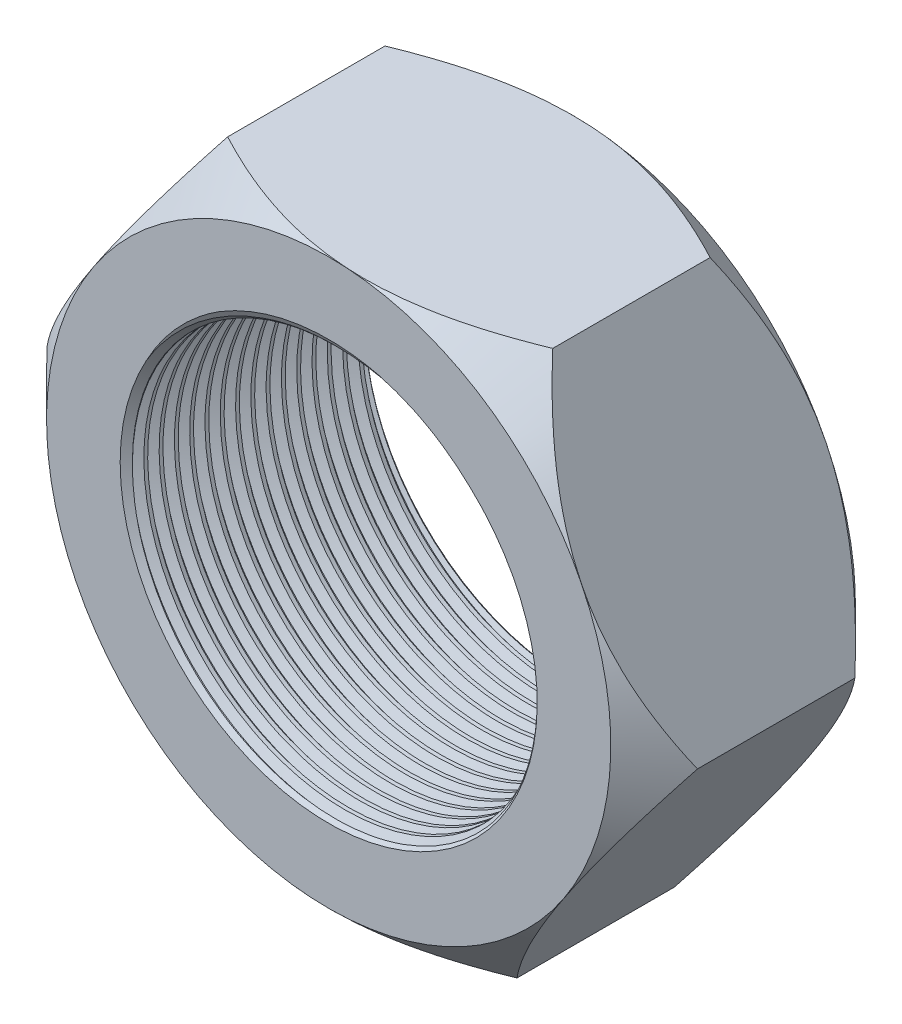
SolidWorks part; units mm, degrees
ref_plane "Front Plane" through (0, 0, 0) normal (0, 0, 1) x (1, 0, 0)
ref_plane "Top Plane" through (0, 0, 0) normal (0, 1, 0) x (1, 0, 0)
ref_plane "Right Plane" through (0, 0, 0) normal (1, 0, 0) x (0, 0, -1)
sketch "Sketch1" plane through (0, 0, 0) normal (0, 0, 1) x (1, 0, 0)
  line L1 (11.8297, -23.8634) -> (26.5812, -1.6869)
  line L2 (26.5812, -1.6869) -> (14.7515, 22.1765)
  line L3 (14.7515, 22.1765) -> (-11.8297, 23.8634)
  line L4 (-11.8297, 23.8634) -> (-26.5812, 1.6869)
  line L5 (-26.5812, 1.6869) -> (-14.7515, -22.1765)
  line L6 (-14.7515, -22.1765) -> (11.8297, -23.8634)
  circle A0 centre (0, 0) radius 23.0663 construction
extrude "Boss-Extrude1" add sketch "Sketch1" along normal blind 20
sketch "Sketch2" plane through (0, 0, 20) normal (0, 0, 1) x (1, 0, 0)
  line L0 (-11.8297, 23.8634) -> (-26.5812, 1.6869) construction
  circle A0 centre (0, 0) radius 23.0663
extrude "Cut-Extrude6" cut sketch "Sketch2" against normal through all draft 45 flip side to cut
ref_plane "Plane1" through (0, 0, 10) normal (0, 0, 1) x (1, 0, 0)
mirror "Mirror3" about plane through (0, 0, 10) normal (0, 0, 1) of "Cut-Extrude6"
sketch "Sketch9" plane through (0, 0, 20) normal (0, 0, 1) x (1, 0, 0)
  circle A0 centre (0, 0) radius 16.5478
extrude "Cut-Extrude10" cut sketch "Sketch9" against normal through all
chamfer "Chamfer1" distance 0.5 angle 45 2 edges at (16.5478, 0, 0) (16.5478, 0, 20)
thread "Thread1" pitch 1.25 method cut profile "Thread Profile2" start angle 0, offset 5, length 0, pitch 1.25, diameter 33.0955
ref_plane "Plane3" through (-16.5478, 0, 24.5) normal (0, -1, 0) x (-1, 0, 0)
sketch "Thread Profile2" plane through (-16.5478, 0, 24.5) normal (0, -1, 0) x (-1, 0, 0)
  line L0 (0, 0) -> (0, 1.25) construction
  line L1 (0, 0) -> (0.6766, 0.3906)
  line L2 (0.6766, 0.3906) -> (0.6766, 0.5469)
  line L3 (0.6766, 0.5469) -> (0, 0.9375)
  line L4 (0.6766, 0.4687) -> (0, 0.4687) construction
  line L11 (0, 0) -> (0, 0.9375)
  point P2 (0, 0)
  dimension "Pitch" = 1.25
  dimension "Profile_Angle" = 60
  dimension "Profile_Land" = 0.1562
  dimension "Profile_Height" = 0.6766
